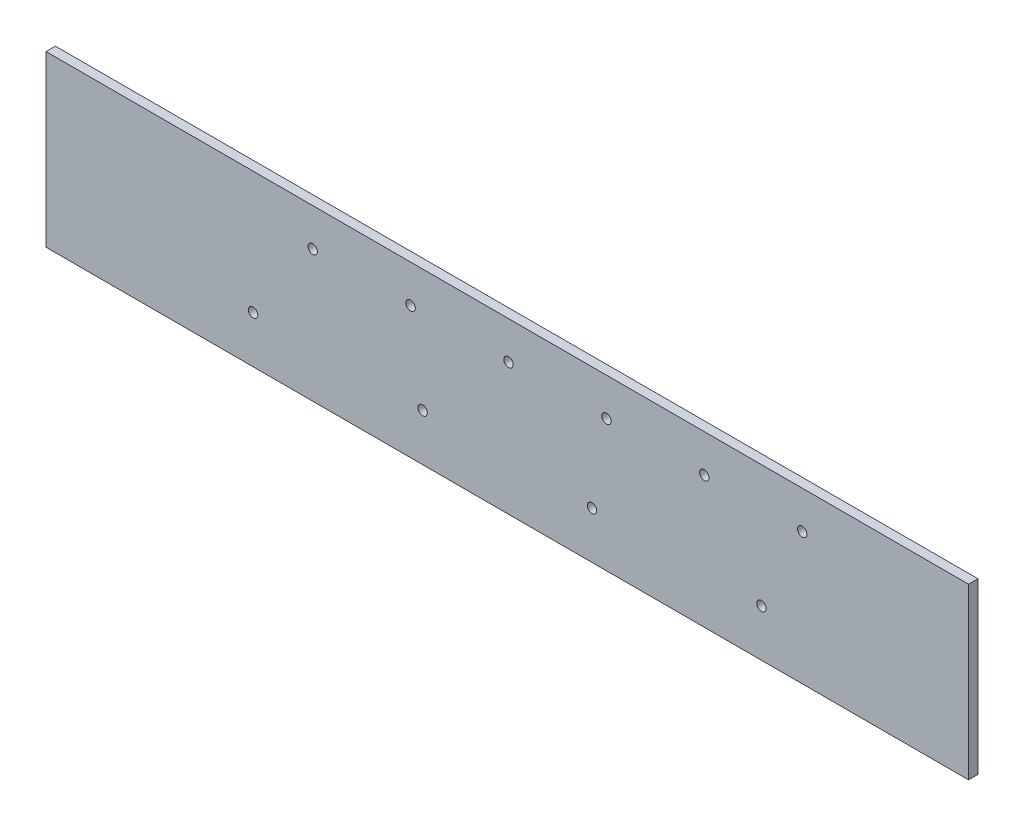
SolidWorks part; units mm, degrees
material "6061 Alloy"
ref_plane "Front Plane" through (0, 0, 0) normal (0, 0, 1) x (1, 0, 0)
ref_plane "Top Plane" through (0, 0, 0) normal (0, 1, 0) x (1, 0, 0)
ref_plane "Right Plane" through (0, 0, 0) normal (1, 0, 0) x (0, 0, -1)
sketch "Sketch1" plane through (0, 0, 457.2) normal (0, 0, 1) x (1, 0, 0)
  line L0 (311.15, 0) -> (311.15, 571.5) construction
  line L1 (-311.15, 114.3) -> (311.15, 114.3)
  line L2 (-311.15, 114.3) -> (-311.15, 0)
  line L3 (-311.15, 0) -> (311.15, 0)
  line L4 (311.15, 114.3) -> (311.15, 0)
  dimension "D1" = 114.3
extrude "Boss-Extrude1" add sketch "Sketch1" along normal blind 6.35
sketch "Sketch2" plane through (0, 0, 463.55) normal (0, 0, 1) x (1, 0, 0)
  point P0 (-131.2597, 88.9)
hole_wizard "1/4 (0.25) Diameter Hole1" positions "Sketch2" profile "Sketch3" hole size "1/4" standard "ANSI Inch" end condition through all
sketch "Sketch3" plane through (-131.2597, 88.9, 463.55) normal (1, 0, 0) x (0, -1, 0)
  line L0 (0, 0) -> (0, 6.35)
  line L1 (0, 6.35) -> (3.175, 6.35)
  line L2 (3.175, 6.35) -> (3.175, 0)
  line L5 (3.175, 0) -> (0, 0)
  line L11 (0, -6.35) -> (0, 107.95) construction
  dimension "Thru Hole Dia." = 6.35
  dimension "Thru Hole Depth" = 6.35
pattern_linear "LPattern1" count 6 spacing 66.04 along (1, 0, 0) of "1/4 (0.25) Diameter Hole1"
sketch "Sketch4" plane through (0, 0, 463.55) normal (0, 0, 1) x (1, 0, 0)
  point P0 (-171.45, 31.75)
hole_wizard "1/4 (0.25) Diameter Hole2" positions "Sketch4" profile "Sketch5" hole size "1/4" standard "ANSI Inch" end condition through all
sketch "Sketch5" plane through (-171.45, 31.75, 463.55) normal (1, 0, 0) x (0, -1, 0)
  line L0 (0, 0) -> (0, 6.35)
  line L1 (0, 6.35) -> (3.175, 6.35)
  line L2 (3.175, 6.35) -> (3.175, 0)
  line L5 (3.175, 0) -> (0, 0)
  line L11 (0, -6.35) -> (0, 107.95) construction
  dimension "Thru Hole Dia." = 6.35
  dimension "Thru Hole Depth" = 6.35
pattern_linear "LPattern2" count 4 spacing 114.3 along (1, 0, 0) of "1/4 (0.25) Diameter Hole2"
